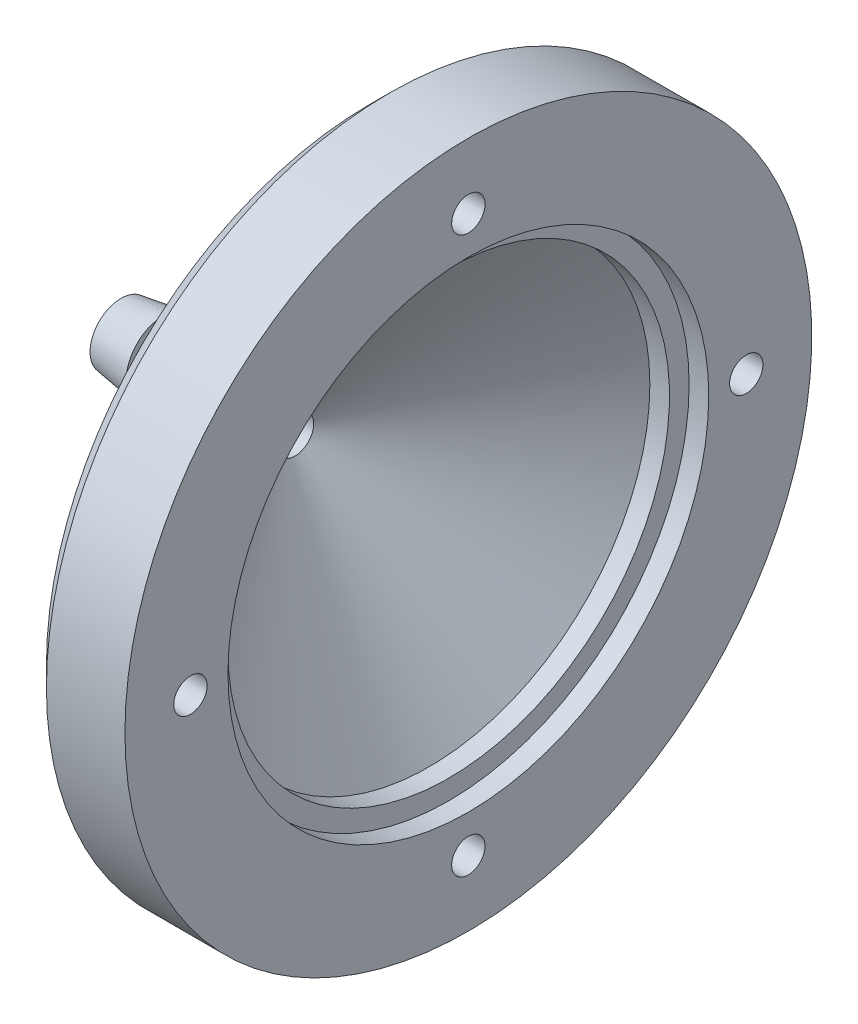
SolidWorks part; units mm, degrees
ref_plane "Front Plane" through (0, 0, 0) normal (0, 0, 1) x (1, 0, 0)
ref_plane "Top Plane" through (0, 0, 0) normal (0, 1, 0) x (1, 0, 0)
ref_plane "Right Plane" through (0, 0, 0) normal (1, 0, 0) x (0, 0, -1)
sketch "Sketch1" plane through (0, 0, 0) normal (0, 0, 1) x (1, 0, 0)
  line L0 (-801.9206, 0) -> (36107.5283, 0) construction
  line L3 (-13.4063, 3.8) -> (-13.4063, 3.15)
  line L8 (-17.7397, 1.9) -> (0, 1.9)
  line L9 (-17.7397, 1.9) -> (-17.7397, 3.15)
  line L10 (17.6645, 24.5) -> (17.6645, 35)
  line L12 (17.6645, 35) -> (7.6645, 35)
  line L16 (17.6645, 24.5) -> (15.6645, 24.5)
  line L17 (15.6645, 24.5) -> (15.6645, 22.5)
  line L18 (7.6645, 35) -> (7.6645, 22.5)
  line L20 (0, 1.9) -> (13.6645, 22.5)
  line L21 (-17.7397, 3.15) -> (-13.4063, 3.8)
  line L22 (13.6645, 22.5) -> (15.6645, 22.5)
  line L23 (-13.4063, 3.15) -> (-9.073, 3.8)
  line L25 (-9.073, 3.15) -> (-4.7397, 3.8)
  line L26 (-9.073, 3.8) -> (-9.073, 3.15)
  line L27 (-4.7397, 3.8) -> (7.6645, 22.5)
  dimension "D3" = 2
  dimension "D2" = 7.6
  dimension "D6" = 3.8
  dimension "D7" = 6.3
  dimension "D1" = 10
  dimension "D5" = 35
  dimension "D8" = 24.5
  dimension "D10" = 2
  dimension "D4" = 5
  dimension "D9" = 2
  dimension "D11" = 13
revolve "Revolve17" add sketch "Sketch1" angle 360 about L0
sketch "Sketch4" plane through (7.6645, 0, 0) normal (-1, 0, 0) x (0, 0, 1)
  circle A0 centre (0, 0) radius 28.325 construction
  point P3 (0, 28.325)
  point P7 (28.325, 0)
  point P12 (-28.325, 0)
  point P13 (0, -28.325)
  point P14 (0, 0)
  point P15 (0, 0)
  point P16 (0, 0)
  point P17 (-28.325, 0)
  dimension "D1" = 56.65
hole_wizard "M3 Clearance Hole1" positions "Sketch4" profile "Sketch5" hole size "M3" standard "ISO"
sketch "Sketch5" plane through (7.6645, -28.325, 0) normal (0, 1, 0) x (0, 0, 1)
  line L0 (0, 0) -> (0, 11.0215)
  line L1 (0, 11.0215) -> (1.7, 10)
  line L2 (1.7, 10) -> (1.7, 0)
  line L5 (1.7, 0) -> (0, 0)
  line L10 (0, 11.0215) -> (-1.7, 10) construction
  line L11 (0, -6.35) -> (0, 107.95) construction
  dimension "Hole Dia." = 3.4
  dimension "Hole Depth" = 10
  dimension "Drill Angle" = 118
chamfer "Chamfer1" distance 2 angle 45 1 edges at (7.6645, 0, 35)
equation "\"D10@Sketch1\"=\"D3@Sketch1\""
equation "\"D9@Sketch1\"=\"D3@Sketch1\""
